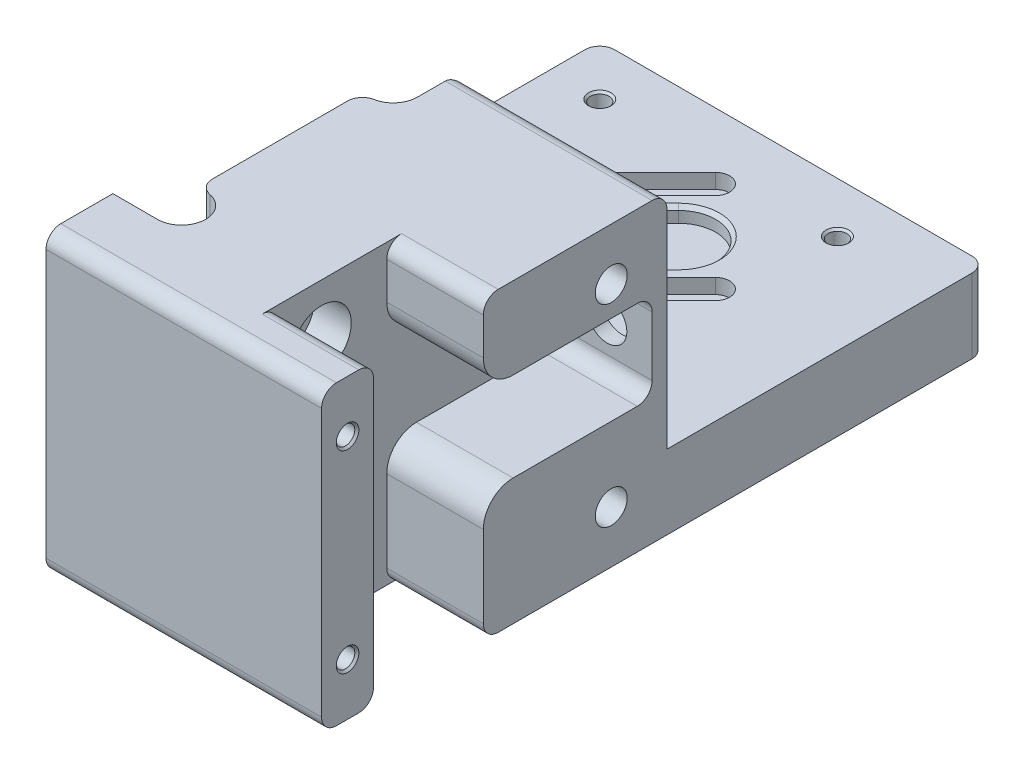
SolidWorks part; units mm, degrees
material "AISI 1045 Steel, cold drawn"
ref_plane "Front Plane" through (0, 0, 0) normal (0, 0, 1) x (1, 0, 0)
ref_plane "Top Plane" through (0, 0, 0) normal (0, 1, 0) x (1, 0, 0)
ref_plane "Right Plane" through (0, 0, 0) normal (1, 0, 0) x (0, 0, -1)
sketch "Sketch1" plane through (0, 0, 0) normal (0, 1, 0) x (1, 0, 0)
  line L0 (-211.9, -221.9) -> (-183.9, -221.9) construction
  line L1 (250, -250) -> (-250, -250)
  line L2 (250, -250) -> (250, 250)
  line L3 (250, 250) -> (-250, 250)
  line L4 (-250, -250) -> (-250, 250)
  line L5 (250, -250) -> (-250, 250) construction
  line L6 (250, 250) -> (-250, -250) construction
  line L7 (-250, -250) -> (-211.9, -250)
  line L8 (-250, -250) -> (-250, -211.9)
  line L9 (-250, -211.9) -> (-211.9, -211.9)
  line L10 (-211.9, -250) -> (-211.9, -211.9)
  line L11 (-211.9, -238.9) -> (-183.9, -238.9)
  line L12 (-211.9, -238.9) -> (-211.9, -204.9)
  line L13 (-211.9, -204.9) -> (-183.9, -204.9)
  line L14 (-183.9, -238.9) -> (-183.9, -204.9)
  line L16 (152.5, 152.5) -> (-152.5, 152.5)
  line L17 (152.5, 152.5) -> (152.5, -152.5)
  line L18 (152.5, -152.5) -> (-152.5, -152.5)
  line L19 (-152.5, 152.5) -> (-152.5, -152.5)
  line L20 (152.5, 152.5) -> (-152.5, -152.5) construction
  line L21 (152.5, -152.5) -> (-152.5, 152.5) construction
  point P0 (0, 0)
  point P15 (-158.3, -233)
  point P16 (-188.9, -188.9)
  point P17 (0, 0)
  point P22 (-181.1218, -181.1218)
  dimension "D1" = 500
  dimension "D2" = 38.1
  dimension "D3" = 28
  dimension "D4" = 17
  dimension "D5" = 20
  dimension "D6" = 91.7
  dimension "D7" = 17
  dimension "D8" = 305
  dimension "D9" = 5
  dimension "D10" = 11
ref_plane "Plane1" through (-188.9, 0, 188.9) normal (-0.7071, 0, 0.7071) x (0.7071, 0, 0.7071)
sketch "Sketch3" plane through (-188.9, 0, 188.9) normal (-0.7071, 0, 0.7071) x (0.7071, 0, 0.7071)
  line L0 (-8.6603, -5) -> (8.6603, -5) construction
  line L1 (0, 0) -> (0, -5) construction
  line L2 (-8.6603, -5) -> (0, 0) construction
  line L3 (-6.7451, -6.607) -> (-8.6603, -5) construction
  line L4 (-6.7451, -6.607) -> (6.7451, -6.607)
  line L5 (-6.7451, -6.607) -> (-6.7451, -16.607)
  line L6 (-6.7451, -16.607) -> (6.7451, -16.607)
  line L7 (6.7451, -6.607) -> (6.7451, -16.607)
  line L8 (10.5754, -16.607) -> (13.5754, -16.607)
  line L9 (-10.5754, -6.607) -> (-13.5754, -6.607)
  line L10 (-10.5754, -6.607) -> (-10.5754, -16.607)
  line L11 (-10.5754, -16.607) -> (-13.5754, -16.607)
  line L12 (-13.5754, -6.607) -> (-13.5754, -16.607)
  line L13 (13.5754, -6.607) -> (13.5754, -16.607)
  line L14 (10.5754, -6.607) -> (13.5754, -6.607)
  line L15 (10.5754, -6.607) -> (10.5754, -16.607)
  circle A0 centre (0, 0) radius 7.5
  circle A1 centre (-8.6603, -5) radius 2.5
  circle A2 centre (8.6603, -5) radius 2.5
  point P20 (-10.5754, -3.393)
  dimension "D1" = 15
  dimension "D2" = 5
  dimension "D3" = 30
  dimension "D4" = 10
  dimension "D5" = 40
  dimension "D6" = 3
extrude "Boss-Extrude1" add sketch "Sketch3" against normal blind 22 contours L9 L12 L11 L10 | L7 L4 L5 L6 | L14 L15 L8 L13 | L4 A0
sketch "Sketch4" plane through (-188.9, 0, 188.9) normal (-0.7071, 0, 0.7071) x (0.7071, 0, 0.7071)
  line L1 (-13.5754, -16.607) -> (13.5754, -16.607)
  line L2 (-13.5754, -16.607) -> (-13.5754, -6.607)
  line L3 (-13.5754, -6.607) -> (13.5754, -6.607)
  line L4 (13.5754, -16.607) -> (13.5754, -6.607)
extrude "Boss-Extrude2" add sketch "Sketch4" along normal blind 3
sketch "Sketch5" plane through (-173.3437, 0, 173.3437) normal (0.7071, 0, -0.7071) x (-0.7071, 0, -0.7071)
  line L1 (-13.5754, -16.607) -> (13.5754, -16.607)
  line L2 (-13.5754, -16.607) -> (-13.5754, -6.607)
  line L3 (-13.5754, -6.607) -> (13.5754, -6.607)
  line L4 (13.5754, -16.607) -> (13.5754, -6.607)
extrude "Boss-Extrude3" add sketch "Sketch5" along normal blind 3
sketch "Sketch7" plane through (0, -6.607, 0) normal (0, 1, 0) x (1, 0, 0)
  line L0 (-188.9, -238.9) -> (-183.9, -238.9)
  line L1 (-211.9, -238.9) -> (-183.9, -238.9) construction
  line L2 (-183.9, -238.9) -> (-183.9, -203.9)
  line L4 (-188.9, -238.9) -> (-188.9, -245.9)
  line L5 (-188.9, -245.9) -> (-146.8, -245.9)
  line L13 (-184.7015, -203.9) -> (-161.6231, -180.8216)
  line L15 (-183.9, -203.9) -> (-200.6206, -203.9)
  line L33 (-200.6206, -203.9) -> (-200.6206, -181.4221)
  line L34 (-200.6206, -181.4221) -> (-178.1426, -203.9)
  line L35 (-211.9, -204.9) -> (-183.9, -204.9) construction
  line L37 (-151.8, -239.88) -> (-164.8, -239.88) construction
  line L38 (-151.8, -239.88) -> (-151.8, -226.12)
  line L39 (-151.8, -226.12) -> (-164.8, -226.12)
  line L40 (-164.8, -239.88) -> (-164.8, -226.12)
  line L41 (-151.8, -239.88) -> (-164.8, -226.12) construction
  line L42 (-151.8, -226.12) -> (-164.8, -239.88) construction
  line L44 (-146.8, -161.6231) -> (-146.8, -245.9)
  line L45 (-164.8, -239.88) -> (-164.8, -240.9)
  line L46 (-164.8, -240.9) -> (-151.8, -240.9)
  line L47 (-151.8, -240.9) -> (-151.8, -239.88)
  line L48 (-181.4221, -200.6206) -> (-200.6206, -181.4221) construction
  line L49 (-181.4221, -200.6206) -> (-161.6231, -180.8216) construction
  line L50 (-161.6231, -180.8216) -> (-180.8216, -161.6231)
  line L51 (-180.8216, -161.6231) -> (-146.8, -161.6231)
  point P17 (-158.3, -233)
  dimension "D3" = 5
  dimension "D4" = 13.76
  dimension "D1" = 5
  dimension "D2" = 1
  dimension "D5" = 13
  dimension "D6" = 7
  dimension "D7" = 5
extrude "Boss-Extrude4" add sketch "Sketch7" against normal up to surface (10 mm away) up to face at (-181.1218, -16.607, 181.1218)
sketch "Sketch13" plane through (0, -6.607, 0) normal (0, 1, 0) x (1, 0, 0)
  line L2 (-181.4221, -196.3779) -> (-181.4221, -203.9) construction
  line L3 (-200.6206, -203.9) -> (-203.9, -203.9)
  line L4 (-200.6206, -203.9) -> (-200.6206, -181.4221)
  line L5 (-180.8216, -161.6231) -> (-200.6206, -181.4221)
  line L7 (-203.9, -203.9) -> (-203.9, -158.3437)
  line L8 (-183.9, -203.9) -> (-200.6206, -203.9) construction
  line L9 (-196.3779, -181.4221) -> (-203.9, -181.4221) construction
  line L10 (-180.8216, -165.8657) -> (-180.8216, -158.3437) construction
  line L11 (-180.8216, -161.6231) -> (-146.8, -161.6231)
  line L12 (-146.8, -161.6231) -> (-146.8, -158.3437)
  line L13 (-146.8, -158.3437) -> (-203.9, -158.3437)
extrude "Boss-Extrude5" add sketch "Sketch13" against normal up to surface (10 mm away) up to face at (-180.1403, -16.607, 209.1187)
sketch "Sketch15" plane through (0, -6.607, 0) normal (0, 1, 0) x (1, 0, 0)
  line L0 (-180.8216, -165.8657) -> (-178.1132, -168.5741) construction
  line L5 (-168.5741, -178.1132) -> (-165.8657, -180.8216) construction
  line L10 (-193.6695, -184.1305) -> (-196.3779, -181.4221) construction
  line L11 (-181.4221, -196.3779) -> (-184.1305, -193.6695) construction
  circle A8 centre (-179.4674, -167.2199) radius 1.9151
  circle A9 centre (-167.2199, -179.4674) radius 1.9151
  circle A10 centre (-195.0237, -182.7763) radius 1.9151
  circle A11 centre (-182.7763, -195.0237) radius 1.9151
extrude "Cut-Extrude4" cut sketch "Sketch15" against normal through all
sketch "Sketch18" plane through (0, -6.607, 0) normal (0, 1, 0) x (1, 0, 0)
  line L0 (-183.9, -203.9) -> (-146.8, -203.9)
  line L1 (-151.8, -226.12) -> (-164.8, -226.12) construction
  line L2 (-164.8, -226.12) -> (-164.8, -240.9) construction
  line L3 (-164.8, -240.9) -> (-151.8, -240.9) construction
  line L4 (-151.8, -240.9) -> (-151.8, -226.12) construction
  line L5 (-151.8, -226.12) -> (-164.8, -226.12)
  line L6 (-164.8, -226.12) -> (-164.8, -240.9)
  line L7 (-164.8, -240.9) -> (-151.8, -240.9)
  line L8 (-146.8, -245.9) -> (-146.8, -158.3437)
  line L9 (-146.8, -158.3437) -> (-203.9, -158.3437)
  line L10 (-203.9, -158.3437) -> (-203.9, -203.9)
  line L11 (-203.9, -203.9) -> (-183.9, -203.9)
  line L12 (-183.9, -203.9) -> (-183.9, -238.9)
  line L13 (-183.9, -238.9) -> (-188.9, -238.9)
  line L14 (-188.9, -238.9) -> (-188.9, -245.9)
  line L15 (-188.9, -245.9) -> (-146.8, -245.9)
  line L16 (-146.8, -245.9) -> (-146.8, -203.9)
  line L20 (-183.9, -203.9) -> (-183.9, -238.9)
  line L21 (-183.9, -238.9) -> (-188.9, -238.9)
  line L22 (-188.9, -238.9) -> (-188.9, -245.9)
  line L23 (-188.9, -245.9) -> (-146.8, -245.9)
  line L24 (-151.8, -240.9) -> (-151.8, -226.12)
  dimension "D1" = 0
extrude "Boss-Extrude6" add sketch "Sketch18" along normal blind 30
hole_wizard "M4 Clearance Hole1" positions "Sketch19" profile "Sketch21" hole size "M4" standard "ANSI Metric" end condition through all
sketch "Sketch19" plane through (-146.8, 0, 0) normal (1, 0, 0) x (0, 0, -1)
  line L1 (-234.9, 16.393) -> (-208.9, 16.393)
  line L2 (-234.9, 16.393) -> (-234.9, -9.607)
  line L3 (-234.9, -9.607) -> (-208.9, -9.607)
  line L4 (-208.9, 16.393) -> (-208.9, -9.607)
  line L6 (-245.9, 23.393) -> (-245.9, -16.607) construction
  line L7 (-238.9, -16.607) -> (-238.9, 23.393) construction
  point P2 (-208.9, -9.607)
  point P124 (-208.9, 16.393)
  point P146 (-245.9, 3.393)
  point P147 (-234.9, 3.393)
  dimension "D1" = 26
  dimension "D2" = 26
  dimension "D3" = 4
sketch "Sketch21" plane through (-146.8, 16.393, 208.9) normal (0, 1, 0) x (0, 0, -1)
  line L0 (0, 0) -> (0, 57.1)
  line L1 (0, 57.1) -> (2.15, 57.1)
  line L2 (2.15, 57.1) -> (2.15, 0)
  line L5 (2.15, 0) -> (0, 0)
  line L11 (0, -6.35) -> (0, 107.95) construction
  dimension "Thru Hole Dia." = 4.3
  dimension "Thru Hole Depth" = 57.1
sketch "Sketch22" plane through (-146.8, 0, 0) normal (1, 0, 0) x (0, 0, -1)
  line L6 (-245.9, 23.393) -> (-245.9, -16.607)
  line L7 (-245.9, -16.607) -> (-158.3437, -16.607)
  line L8 (-158.3437, -16.607) -> (-158.3437, -6.607)
  line L9 (-158.3437, -6.607) -> (-203.9, -6.607)
  line L10 (-203.9, -6.607) -> (-203.9, 23.393)
  line L11 (-203.9, 23.393) -> (-245.9, 23.393)
  line L12 (-245.9, 23.393) -> (-245.9, -16.607)
  line L13 (-245.9, -16.607) -> (-158.3437, -16.607)
  line L14 (-158.3437, -16.607) -> (-158.3437, -6.607)
  line L15 (-158.3437, -6.607) -> (-203.9, -6.607)
  line L16 (-203.9, -6.607) -> (-203.9, 23.393)
  line L17 (-203.9, 23.393) -> (-245.9, 23.393)
  dimension "D1" = 0
extrude "Cut-Extrude7" cut sketch "Sketch22" against normal blind 5
sketch "Sketch17" plane through (0, -6.607, 0) normal (0, 1, 0) x (1, 0, 0)
  line L0 (-185.8914, -176.3523) -> (-176.3523, -185.8914) construction
  line L1 (-178.1132, -168.5741) -> (-193.6695, -184.1305) construction
  line L2 (-168.5741, -178.1132) -> (-184.1305, -193.6695) construction
  line L3 (-186.4251, -186.4251) -> (-175.8185, -175.8185) construction
  line L4 (-189.9607, -182.8896) -> (-179.3541, -172.283)
  line L5 (-182.8896, -189.9607) -> (-172.283, -179.3541)
  arc A1 (-189.9607, -182.8896) -> (-182.8896, -189.9607) centre (-186.4251, -186.4251) ccw
  arc A2 (-172.283, -179.3541) -> (-179.3541, -172.283) centre (-175.8185, -175.8185) ccw
  point P8 (-181.1218, -181.1218)
  dimension "D1" = 5
  dimension "D2" = 15
extrude "Cut-Extrude6" cut sketch "Sketch17" against normal blind 2
hole_wizard "M3x0.5 Tapped Hole2" positions "Sketch25" profile "Sketch26" tap size "M3x0.5" standard "ANSI Metric" end condition through all
sketch "Sketch25" plane through (0, -6.607, 0) normal (0, 1, 0) x (1, 0, 0)
  line L1 (-197.1218, -165.1218) -> (-165.1218, -165.1218)
  line L2 (-197.1218, -165.1218) -> (-197.1218, -197.1218)
  line L3 (-197.1218, -197.1218) -> (-165.1218, -197.1218)
  line L4 (-165.1218, -165.1218) -> (-165.1218, -197.1218)
  line L6 (-197.1218, -165.1218) -> (-165.1218, -197.1218) construction
  line L7 (-189.9607, -189.9607) -> (-172.283, -172.283) construction
  arc A2 (-189.9607, -182.8896) -> (-182.8896, -189.9607) centre (-186.4251, -186.4251) ccw construction
  arc A3 (-172.283, -179.3541) -> (-179.3541, -172.283) centre (-175.8185, -175.8185) ccw construction
  point P1 (-197.1218, -165.1218)
  point P2 (-165.1218, -197.1218)
  point P59 (-197.1218, -197.1218)
  point P60 (-165.1218, -165.1218)
  point P88 (-181.1218, -181.1218)
  point P89 (-181.1218, -181.1218)
  dimension "D1" = 32
sketch "Sketch26" plane through (-197.1218, -6.607, 165.1218) normal (1, 0, 0) x (0, 0, 1)
  line L0 (0, 0) -> (0, 10)
  line L1 (0, 10) -> (1.25, 10)
  line L2 (1.25, 10) -> (1.25, 0.275)
  line L3 (1.25, 0.275) -> (1.525, 0)
  line L5 (1.525, 0) -> (0, 0)
  line L6 (-1.25, 0.275) -> (-1.525, 0) construction
  line L11 (0, -6.35) -> (0, 107.95) construction
  dimension "Thru Tap Drill Dia." = 2.5
  dimension "Thru Tap Drill Depth" = 10
  dimension "Near C'Sink Dia." = 3.05
  dimension "Near C'Sink Angle" = 90
cosmetic thread "Hole Thread3" parameters "D2"=3
cosmetic thread "Hole Thread4" parameters "D2"=3
cosmetic thread "Hole Thread5" parameters "D2"=3
cosmetic thread "Hole Thread6" parameters "D2"=3
sketch "Sketch43" plane through (0, 0, 203.9) normal (0, 0, -1) x (-1, 0, 0)
  line L4 (151.8, 23.393) -> (151.8, -6.607)
  line L5 (151.8, -6.607) -> (183.9, -6.607)
  line L6 (183.9, -6.607) -> (183.9, 23.393)
  line L7 (183.9, 23.393) -> (151.8, 23.393)
  line L8 (151.8, 23.393) -> (151.8, -6.607)
  line L9 (151.8, -6.607) -> (183.9, -6.607)
  line L10 (183.9, -6.607) -> (183.9, 23.393)
  line L11 (183.9, 23.393) -> (151.8, 23.393)
  dimension "D1" = 0
extrude "Boss-Extrude9" add sketch "Sketch43" along normal blind 2.5
sketch "Sketch27" plane through (-151.8, 0, 0) normal (1, 0, 0) x (0, 0, -1)
  line L0 (-226.12, -16.607) -> (-226.12, 23.393) construction
  line L1 (-226.12, 12.393) -> (-203.4, 12.393)
  line L2 (-226.12, 12.393) -> (-226.12, 0.393)
  line L3 (-226.12, 0.393) -> (-203.4, 0.393)
  line L4 (-203.4, 12.393) -> (-203.4, 0.393)
  line L6 (-201.4, 23.393) -> (-201.4, -6.607) construction
  circle A0 centre (-208.9, 16.393) radius 2.15 construction
  dimension "D3" = 4
  dimension "D1" = 12
  dimension "D2" = 2
extrude "Cut-Extrude9" cut sketch "Sketch27" against normal up to surface (13 mm away) up to face at (-164.8, 3.393, 233.51)
fillet "Fillet1" radius 2 2 edges at (-158.3, 0.393, 203.4) (-158.3, 12.393, 203.4)
fillet "Fillet2" radius 4 2 edges at (-158.3, 0.393, 226.12) (-158.3, 12.393, 226.12)
hole_wizard "CBORE for M4 SHCS1" positions "Sketch29" profile "Sketch30" counterbore size "M4" standard "ANSI Metric" end condition through all
sketch "Sketch29" plane through (-164.8, 0, 0) normal (1, 0, 0) x (0, 0, -1)
  point P0 (-234.9, 16.393)
  point P3 (-234.9, -9.607)
sketch "Sketch30" plane through (-164.8, 16.393, 234.9) normal (0, 1, 0) x (0, 0, -1)
  line L0 (0, 0) -> (0, 39.1)
  line L1 (0, 39.1) -> (2.15, 39.1)
  line L3 (2.15, 39.1) -> (2.15, 5)
  line L4 (2.15, 5) -> (4, 5)
  line L5 (4, 5) -> (4, 0)
  line L7 (4, 0) -> (0, 0)
  line L11 (0, -6.35) -> (0, 107.95) construction
  dimension "Thru Hole Dia." = 4.3
  dimension "Thru Hole Depth" = 39.1
  dimension "C'Bore Dia." = 8
  dimension "C'Bore Depth" = 5
sketch "Sketch31" plane through (0, 0, 245.9) normal (0, 0, 1) x (1, 0, 0)
  line L4 (-188.9, -16.607) -> (-151.8, -16.607)
  line L5 (-151.8, -16.607) -> (-151.8, 23.393)
  line L6 (-151.8, 23.393) -> (-188.9, 23.393)
  line L7 (-188.9, 23.393) -> (-188.9, -16.607)
  line L8 (-188.9, -16.607) -> (-151.8, -16.607)
  line L9 (-151.8, -16.607) -> (-151.8, 23.393)
  line L10 (-151.8, 23.393) -> (-188.9, 23.393)
  line L11 (-188.9, 23.393) -> (-188.9, -16.607)
  dimension "D1" = 0
extrude "Boss-Extrude8" add sketch "Sketch31" along normal blind 2
hole_wizard "M3x0.5 Tapped Hole3" positions "Sketch34" profile "Sketch35" tap size "M3x0.5" standard "ANSI Metric"
sketch "Sketch34" plane through (-151.8, 0, 0) normal (1, 0, 0) x (0, 0, -1)
  line L1 (-234.9, 16.393) -> (-244.4, 16.393)
  line L2 (-234.9, 16.393) -> (-234.9, -9.607)
  line L3 (-234.9, -9.607) -> (-244.4, -9.607)
  line L4 (-244.4, 16.393) -> (-244.4, -9.607)
  line L6 (-240.9, 3.393) -> (-247.9, 3.393) construction
  line L7 (-240.9, -16.607) -> (-240.9, 23.393) construction
  line L8 (-247.9, -16.607) -> (-247.9, 23.393) construction
  point P2 (-244.4, -9.607)
  point P114 (-244.4, 16.393)
  point P129 (-244.4, 3.393)
sketch "Sketch35" plane through (-151.8, 16.393, 244.4) normal (0, 1, 0) x (0, 0, -1)
  line L0 (0, 0) -> (0, 9.2511)
  line L1 (0, 9.2511) -> (1.25, 8.5)
  line L2 (1.25, 8.5) -> (1.25, 0.275)
  line L3 (1.25, 0.275) -> (1.525, 0)
  line L5 (1.525, 0) -> (0, 0)
  line L6 (-1.25, 0.275) -> (-1.525, 0) construction
  line L10 (0, 9.2511) -> (-1.25, 8.5) construction
  line L11 (0, -6.35) -> (0, 107.95) construction
  dimension "Tap Drill Dia." = 2.5
  dimension "Tap Drill Depth" = 8.5
  dimension "Near C'Sink Dia." = 3.05
  dimension "Near C'Sink Angle" = 90
  dimension "Drill Angle" = 118
cosmetic thread "Hole Thread1" parameters "D1"=6, "D2"=3
cosmetic thread "Hole Thread2" parameters "D1"=6, "D2"=3
fillet "Fillet4" radius 2 10 edges at (-203.9, -11.607, 203.9) (-203.9, -11.607, 158.3437) (-151.8, -11.607, 158.3437) (-158.3, -16.607, 240.9) (-158.3, -16.607, 226.12) (-170.35, -16.607, 247.9) (-158.3, 23.393, 226.12) (-158.3, 23.393, 240.9) (-170.35, 23.393, 247.9) (-167.85, 23.393, 201.4)
sketch "Sketch36" plane through (0, 23.393, 0) normal (0, 1, 0) x (1, 0, 0)
  line L6 (-183.9, -238.9) -> (-188.9, -238.9) construction
  line L7 (-183.9, -203.4) -> (-183.9, -238.9) construction
  line L10 (-183.9, -203.9) -> (-201.9, -203.9) construction
  line L12 (-182.9, -232.4) -> (-183.9, -232.4)
  line L13 (-183.9, -232.4) -> (-183.9, -238.9)
  line L14 (-183.9, -238.9) -> (-182.9, -238.9)
  line L20 (-183.9, -210.4) -> (-183.9, -201.4)
  line L21 (-182.9, -210.4) -> (-183.9, -210.4)
  line L22 (-179.65, -207.15) -> (-179.65, -203.4)
  line L23 (-183.9, -201.4) -> (-151.8, -201.4) construction
  line L24 (-177.65, -201.4) -> (-183.9, -201.4)
  line L25 (-183.9, -203.4) -> (-183.9, -238.9) construction
  line L26 (-151.8, -201.4) -> (-183.9, -201.4) construction
  arc A1 (-182.9, -238.9) -> (-182.9, -232.4) centre (-182.9, -235.65) ccw
  arc A4 (-179.65, -207.15) -> (-182.9, -210.4) centre (-182.9, -207.15) cw
  arc A5 (-179.65, -203.4) -> (-177.65, -201.4) centre (-177.65, -203.4) cw
  dimension "D1" = 3.25
  dimension "D2" = 3.25
  dimension "D4" = 2
  dimension "D3" = 1
extrude "Cut-Extrude10" cut sketch "Sketch36" against normal up to surface (30 mm away) up to face at (-197.1218, -6.607, 166.6468)
sketch "Sketch44" plane through (0, -6.607, 0) normal (0, 1, 0) x (1, 0, 0)
  line L0 (-183.9, -210.4) -> (-182.9, -210.4) construction
  line L1 (-183.9, -210.4) -> (-183.9, -203.9) construction
  line L2 (-183.9, -210.4) -> (-182.9, -210.4)
  line L3 (-182.9, -232.4) -> (-183.9, -232.4)
  line L4 (-183.9, -232.4) -> (-183.9, -238.9)
  line L5 (-183.9, -238.9) -> (-182.9, -238.9)
  line L6 (-182.9, -232.4) -> (-183.9, -232.4)
  line L7 (-183.9, -232.4) -> (-183.9, -238.9)
  line L8 (-183.9, -238.9) -> (-182.9, -238.9)
  line L9 (-183.9, -210.4) -> (-183.9, -203.9)
  line L13 (-183.9, -203.9) -> (-182.9, -203.9)
  arc A0 (-182.9, -210.4) -> (-179.65, -207.15) centre (-182.9, -207.15) ccw construction
  arc A1 (-182.9, -238.9) -> (-182.9, -232.4) centre (-182.9, -235.65) ccw
  arc A2 (-182.9, -238.9) -> (-182.9, -232.4) centre (-182.9, -235.65) ccw
  arc A3 (-182.9, -210.4) -> (-182.9, -203.9) centre (-182.9, -207.15) ccw
  dimension "D1" = 0
extrude "Cut-Extrude12" cut sketch "Sketch44" against normal up to surface (10 mm away) up to face at (-197.1218, -16.607, 166.3718)
fillet "Fillet5" radius 2 2 edges at (-183.9, 3.393, 232.4) (-183.9, 3.393, 210.4)
hole_wizard "M5 Clearance Hole1" positions "Sketch40" profile "Sketch42" hole size "M5" standard "ANSI Metric" end condition up to next
sketch "Sketch40" plane through (0, 0, 201.4) normal (0, 0, -1) x (-1, 0, 0)
  line L0 (151.8, 6.393) -> (157.85, 6.393) construction
  line L3 (164.8, 12.393) -> (151.8, 12.393) construction
  line L4 (151.8, 21.393) -> (151.8, -6.607) construction
  point P0 (157.85, 6.393)
  dimension "D1" = 6.05
  dimension "D2" = 6
sketch "Sketch42" plane through (-157.85, 6.393, 201.4) normal (1, 0, 0) x (0, 1, 0)
  line L0 (0, 0) -> (0, 2)
  line L1 (0, 2) -> (2.65, 2)
  line L2 (2.65, 2) -> (2.65, 0)
  line L5 (2.65, 0) -> (0, 0)
  line L11 (0, -6.35) -> (0, 107.95) construction
  dimension "Thru Hole Dia." = 5.3
  dimension "Thru Hole Depth" = 2
sketch "Sketch45" plane through (0, -16.607, 0) normal (0, -1, 0) x (1, 0, 0)
  line L0 (-180.8216, 165.8657) -> (-196.3779, 181.4221) construction
  line L1 (-178.1132, 168.5741) -> (-193.6695, 184.1305) construction
  line L2 (-165.8657, 180.8216) -> (-181.4221, 196.3779)
  line L3 (-184.1305, 193.6695) -> (-168.5741, 178.1132)
  line L4 (-165.8657, 180.8216) -> (-181.4221, 196.3779)
  line L5 (-184.1305, 193.6695) -> (-168.5741, 178.1132)
  line L6 (-180.8216, 165.8657) -> (-196.3779, 181.4221)
  line L7 (-178.1132, 168.5741) -> (-193.6695, 184.1305)
  arc A0 (-180.8216, 165.8657) -> (-178.1132, 168.5741) centre (-179.4674, 167.2199) ccw construction
  arc A1 (-193.6695, 184.1305) -> (-196.3779, 181.4221) centre (-195.0237, 182.7763) ccw construction
  arc A2 (-168.5741, 178.1132) -> (-165.8657, 180.8216) centre (-167.2199, 179.4674) ccw
  arc A3 (-181.4221, 196.3779) -> (-184.1305, 193.6695) centre (-182.7763, 195.0237) ccw
  arc A4 (-168.5741, 178.1132) -> (-165.8657, 180.8216) centre (-167.2199, 179.4674) ccw
  arc A5 (-181.4221, 196.3779) -> (-184.1305, 193.6695) centre (-182.7763, 195.0237) ccw
  arc A6 (-180.8216, 165.8657) -> (-178.1132, 168.5741) centre (-179.4674, 167.2199) ccw
  arc A7 (-193.6695, 184.1305) -> (-196.3779, 181.4221) centre (-195.0237, 182.7763) ccw
  dimension "D1" = 0
extrude "Boss-Extrude10" add sketch "Sketch45" against normal up to surface (8 mm away) up to face at (-181.1218, -8.607, 181.1218)
mirror "Mirror1" [suppressed]
cosmetic thread "Hole Thread7" [suppressed] parameters "D2"=3
cosmetic thread "Hole Thread8" [suppressed] parameters "D2"=3
cosmetic thread "Hole Thread9" [suppressed] parameters "D1"=6, "D2"=3
cosmetic thread "Hole Thread10" [suppressed] parameters "D1"=6, "D2"=3
cosmetic thread "Hole Thread11" [suppressed] parameters "D2"=3
cosmetic thread "Hole Thread12" [suppressed] parameters "D2"=3
delete or keep bodies "Body-Delete/Keep 1" [suppressed] type delete bodies bodies 156
chamfer "Chamfer1" distance 0.5 angle 45 4 edges at (-172.283, -6.607, 172.283) (-184.6574, -6.607, 177.5863) (-177.5863, -6.607, 184.6574) (-189.9607, -6.607, 189.9607)
